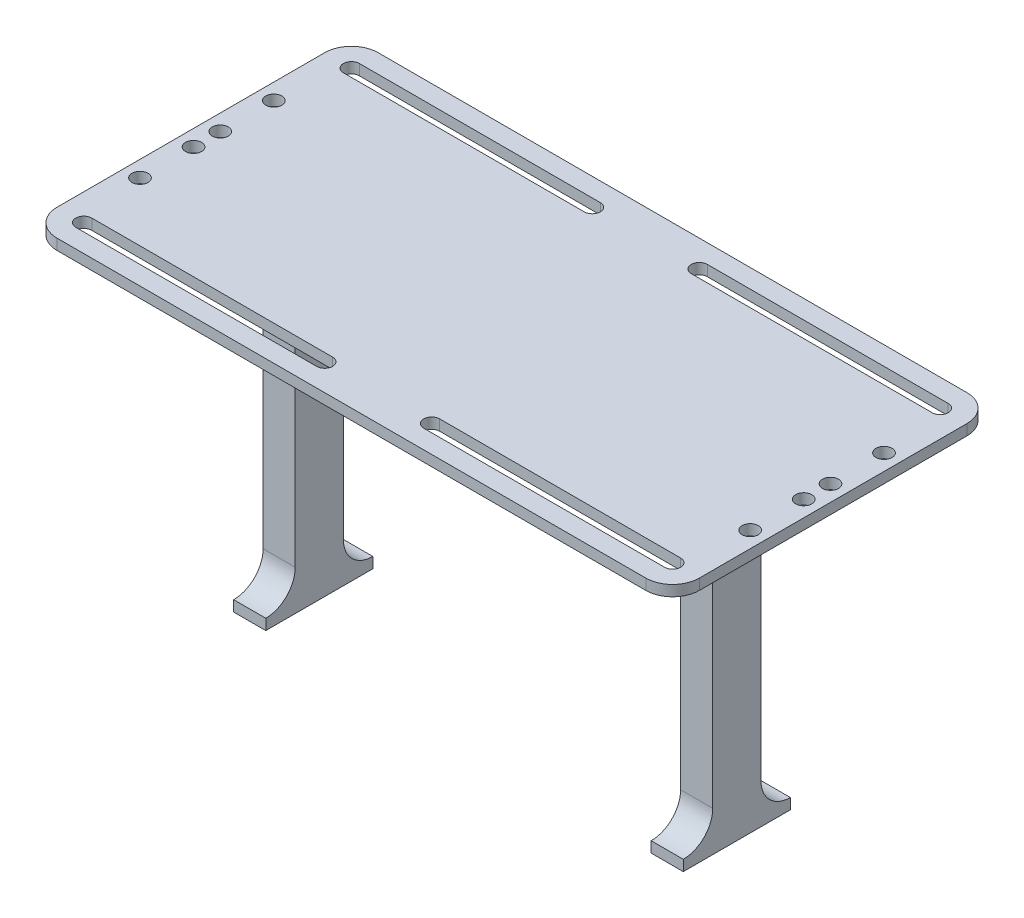
SolidWorks part; units mm, degrees
ref_plane "Front Plane" through (0, 0, 0) normal (0, 0, 1) x (1, 0, 0)
ref_plane "Top Plane" through (0, 0, 0) normal (0, 1, 0) x (1, 0, 0)
ref_plane "Right Plane" through (0, 0, 0) normal (1, 0, 0) x (0, 0, -1)
sketch "Sketch1" plane through (0, 0, 0) normal (0, 1, 0) x (1, 0, 0)
  line L0 (0, -1.9979) -> (0, 3.4727) construction
  line L1 (42, -4.5) -> (36, -4.5)
  line L2 (-42, 4.5) -> (-36, 4.5)
  line L3 (-42, 4.5) -> (-42, -4.5)
  line L4 (-42, -4.5) -> (-36, -4.5)
  line L5 (-36, 4.5) -> (-36, -4.5)
  line L6 (-42, 4.5) -> (-36, -4.5) construction
  line L7 (-42, -4.5) -> (-36, 4.5) construction
  line L8 (36, 4.5) -> (36, -4.5)
  line L9 (42, 4.5) -> (36, 4.5)
  line L10 (42, 4.5) -> (42, -4.5)
  circle A0 centre (-39, 0) radius 1.4
  circle A1 centre (39, 0) radius 1.4
  dimension "D1" = 2.8
  dimension "D2" = 78
  dimension "D3" = 6
  dimension "D4" = 9
extrude "Boss-Extrude1" add sketch "Sketch1" along normal blind 60 contours L3 L2 L5 L4 | L1 L8 L9 L10
sketch "Sketch2" plane through (0, 0, 0) normal (0, -1, 0) x (1, 0, 0)
  line L0 (0, 0) -> (0, 22.5272) construction
  line L1 (-42, 10) -> (-36, 10)
  line L2 (-42, 10) -> (-42, -10)
  line L3 (-42, -10) -> (-36, -10)
  line L4 (-36, 10) -> (-36, -10)
  line L5 (-36, -4.5) -> (-36, 4.5) construction
  line L6 (-42, -4.5) -> (-42, 4.5) construction
  line L7 (0, 0) -> (5.7315, 0) construction
  line L8 (42, -10) -> (36, -10)
  line L9 (36, 10) -> (36, -10)
  line L10 (42, 10) -> (36, 10)
  line L11 (42, 10) -> (42, -10)
  point P12 (-36, 0)
  dimension "D1" = 20
extrude "Boss-Extrude2" add sketch "Sketch2" along normal blind 2
sketch "Sketch3" plane through (0, -2, 0) normal (0, -1, 0) x (1, 0, 0)
  line L4 (-42, -4.5) -> (-36, -4.5)
  line L5 (-36, -4.5) -> (-36, 4.5)
  line L6 (-36, 4.5) -> (-42, 4.5)
  line L7 (-42, 4.5) -> (-42, -4.5)
  line L8 (-42, -4.5) -> (-36, -4.5)
  line L9 (-36, -4.5) -> (-36, 4.5)
  line L10 (-36, 4.5) -> (-42, 4.5)
  line L11 (-42, 4.5) -> (-42, -4.5)
  line L12 (42, 4.5) -> (36, 4.5)
  line L13 (36, 4.5) -> (36, -4.5)
  line L14 (36, -4.5) -> (42, -4.5)
  line L15 (42, -4.5) -> (42, 4.5)
  line L16 (42, 4.5) -> (36, 4.5)
  line L17 (36, 4.5) -> (36, -4.5)
  line L18 (36, -4.5) -> (42, -4.5)
  line L19 (42, -4.5) -> (42, 4.5)
  circle A1 centre (39, 0) radius 1.4
  circle A2 centre (39, 0) radius 1.4
  circle A3 centre (-39, 0) radius 1.4
  circle A4 centre (-39, 0) radius 1.4
  dimension "D1" = 0
  dimension "D2" = 0
  dimension "D3" = 0
  dimension "D4" = 0
extrude "Cut-Extrude1" cut sketch "Sketch3" against normal blind 6 contours A4 | A2
fillet "Fillet1" radius 5.5 2 edges at (-39, 0, -4.5) (-39, 0, 4.5)
fillet "Fillet2" radius 5.5 2 edges at (39, 0, -4.5) (39, 0, 4.5)
sketch "Sketch4" plane through (0, 60, 0) normal (0, 1, 0) x (1, 0, 0)
  line L0 (-60, 0) -> (60, 0) construction
  line L1 (-55, 30) -> (55, 30)
  line L2 (-60, 25) -> (-60, -25)
  line L3 (-55, -30) -> (55, -30)
  line L4 (60, 25) -> (60, -25)
  line L5 (-60, 30) -> (60, -30) construction
  line L6 (-60, -30) -> (60, 30) construction
  line L7 (0, -30) -> (0, 30) construction
  line L8 (55, 25) -> (10, 25) construction
  line L11 (55, 23.5) -> (10, 23.5)
  line L14 (-55, -25) -> (-10, -25) construction
  line L15 (-55, -23.5) -> (-10, -23.5)
  line L16 (-55, -26.5) -> (-10, -26.5)
  line L17 (55, 26.5) -> (10, 26.5)
  line L20 (-60, 30) -> (60, -30) construction
  line L21 (-60, -30) -> (60, 30) construction
  line L22 (-55, 30) -> (55, 30)
  line L23 (55, -25) -> (10, -25) construction
  line L26 (-55, 25) -> (-10, 25) construction
  line L27 (-55, 23.5) -> (-10, 23.5)
  line L28 (-55, 26.5) -> (-10, 26.5)
  line L29 (55, -23.5) -> (10, -23.5)
  line L30 (55, -26.5) -> (10, -26.5)
  arc A0 (55, 30) -> (60, 25) centre (55, 25) cw
  arc A1 (-60, -25) -> (-55, -30) centre (-55, -25) ccw
  arc A2 (-55, 30) -> (-60, 25) centre (-55, 25) ccw
  arc A3 (55, -30) -> (60, -25) centre (55, -25) ccw
  arc A8 (-55, -23.5) -> (-55, -26.5) centre (-55, -25) ccw
  arc A9 (-10, -26.5) -> (-10, -23.5) centre (-10, -25) ccw
  circle A10 centre (-57, -2.5) radius 1.5
  circle A11 centre (-57, -12.5) radius 1.5
  circle A16 centre (57, -12.5) radius 1.5
  circle A17 centre (57, -2.5) radius 1.5
  circle A18 centre (57, 2.5) radius 1.5
  circle A19 centre (57, 12.5) radius 1.5
  circle A22 centre (-57, 12.5) radius 1.5
  circle A23 centre (-57, 2.5) radius 1.5
  arc A24 (55, 30) -> (60, 25) centre (55, 25) cw
  arc A25 (-60, 25) -> (-55, 30) centre (-55, 25) cw
  arc A28 (-55, 23.5) -> (-55, 26.5) centre (-55, 25) cw
  arc A29 (-10, 26.5) -> (-10, 23.5) centre (-10, 25) cw
  circle A30 centre (-57, -22.5) radius 1.5 [skipped]
  arc A31 (55, 23.5) -> (55, 26.5) centre (55, 25) ccw
  arc A32 (10, 26.5) -> (10, 23.5) centre (10, 25) ccw
  arc A33 (55, -23.5) -> (55, -26.5) centre (55, -25) cw
  arc A34 (10, -26.5) -> (10, -23.5) centre (10, -25) cw
  point P0 (0, 0)
  point P22 (40.5771, -21.7118)
  point P23 (-10.5349, 27.3757)
  point P25 (32.5, 25)
  point P32 (32.5, -25)
  point P39 (-32.5, -25)
  point P85 (-32.5, 25)
  dimension "D3" = 5
  dimension "D4" = 10
  dimension "D9" = 3
  dimension "D10" = 5
  dimension "D1" = 120
  dimension "D2" = 60
  dimension "D5" = 5
  dimension "D6" = 3
  dimension "D8" = 3
  dimension "D13" = 5
extrude "Boss-Extrude4" add sketch "Sketch4" along normal blind 2
fillet "Fillet4" radius 10 4 edges at (39, 60, 4.5) (39, 60, -4.5) (-39, 60, -4.5) (-39, 60, 4.5)
